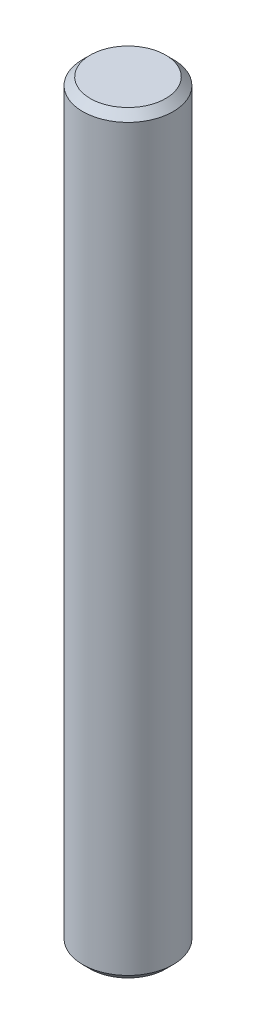
SolidWorks part; units mm, degrees
ref_plane "Спереди" through (0, 0, 0) normal (0, 0, 1) x (1, 0, 0)
ref_plane "Сверху" through (0, 0, 0) normal (0, 1, 0) x (1, 0, 0)
ref_plane "Справа" through (0, 0, 0) normal (1, 0, 0) x (0, 0, -1)
sketch "Эскиз1" plane through (0, 0, 0) normal (0, 1, 0) x (1, 0, 0)
  circle A0 centre (0, 0) radius 3
  dimension "D1" = 6
extrude "Бобышка-Вытянуть1" add sketch "Эскиз1" along normal blind 25 and the other way blind 25
chamfer "Фаска1" distance 0.5 angle 45 2 edges at (0, 25, 3) (0, -25, 3)
